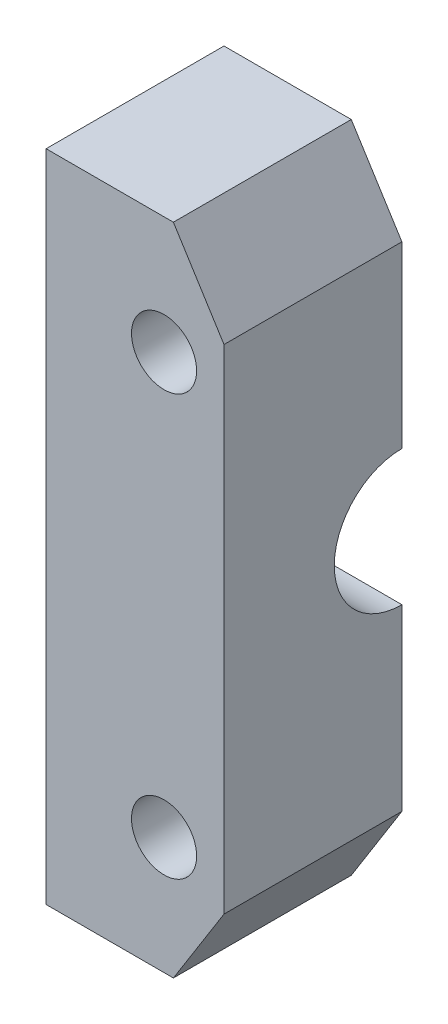
SolidWorks part; units mm, degrees
ref_plane "Front Plane" through (0, 0, 0) normal (0, 0, 1) x (1, 0, 0)
ref_plane "Top Plane" through (0, 0, 0) normal (0, 1, 0) x (1, 0, 0)
ref_plane "Right Plane" through (0, 0, 0) normal (1, 0, 0) x (0, 0, -1)
sketch "Sketch1" plane through (0, 0, 0) normal (0, 0, 1) x (1, 0, 0)
  line L1 (81.54, 23.365) -> (94.24, 23.365)
  line L2 (81.54, 23.365) -> (81.54, -23.365)
  line L3 (81.54, -23.365) -> (94.24, -23.365)
  line L4 (94.24, 23.365) -> (94.24, -23.365)
  line L9 (94.24, 4.826) -> (94.24, 17.6074)
  line L10 (94.24, 17.6074) -> (90.6266, 23.365)
  line L11 (77.2278, 38.2924) -> (72.7482, 36.0713)
  line L12 (72.7482, -36.0713) -> (77.2278, -38.2924)
  line L13 (90.6266, -23.365) -> (94.24, -17.6074)
  line L14 (94.24, -17.6074) -> (94.24, -4.826)
  line L15 (94.24, -4.826) -> (86.49, -4.826)
  line L16 (86.49, -4.826) -> (86.49, 4.826)
  line L17 (86.49, 4.826) -> (94.24, 4.826)
  line L18 (94.24, 4.826) -> (94.24, 17.6074)
  line L19 (94.24, 17.6074) -> (90.6266, 23.365)
  line L20 (77.2278, 38.2924) -> (72.7482, 36.0713)
  line L21 (72.7482, -36.0713) -> (77.2278, -38.2924)
  line L22 (90.6266, -23.365) -> (94.24, -17.6074)
  line L23 (94.24, -17.6074) -> (94.24, -4.826)
  line L24 (94.24, -4.826) -> (86.49, -4.826)
  line L25 (86.49, -4.826) -> (86.49, 4.826)
  line L26 (86.49, 4.826) -> (94.24, 4.826)
  circle A2 centre (89.96, 15) radius 2.325
  arc A3 (77.2278, 38.2924) -> (90.6266, 23.365) centre (110.7726, 54.9252) ccw
  arc A4 (72.7482, -36.0713) -> (72.7482, 36.0713) centre (0, 0) ccw
  arc A5 (90.6266, -23.365) -> (77.2278, -38.2924) centre (110.7726, -54.9252) ccw
  arc A6 (77.2278, 38.2924) -> (90.6266, 23.365) centre (110.7726, 54.9252) ccw
  arc A7 (72.7482, -36.0713) -> (72.7482, 36.0713) centre (0, 0) ccw
  arc A8 (90.6266, -23.365) -> (77.2278, -38.2924) centre (110.7726, -54.9252) ccw
  circle A9 centre (89.96, -15) radius 2.325
  circle A10 centre (89.96, 15) radius 2.5527 construction
  circle A11 centre (89.96, -15) radius 2.5527 construction
  dimension "D2" = 12.7
  dimension "D1" = 0
extrude "Boss-Extrude1" add sketch "Sketch1" along normal blind 12.7 contours L25 L26 L4 L19 L1 L2 L3 L22 L24 A9 A2 | L26 L25 L24 L4 region at (86.0833, 22.8808, 0) region at (90.365, 0, 0)
sketch "Sketch2" plane through (94.24, 0, 0) normal (1, 0, 0) x (0, 0, -1)
  line L4 (0, -17.6074) -> (0, 17.6074)
  line L5 (0, 17.6074) -> (-12.7, 17.6074)
  line L6 (-12.7, 17.6074) -> (-12.7, -17.6074)
  line L7 (-12.7, -17.6074) -> (0, -17.6074)
  line L8 (0, -17.6074) -> (0, 17.6074)
  line L9 (0, 17.6074) -> (-12.7, 17.6074)
  line L10 (-12.7, 17.6074) -> (-12.7, -17.6074)
  line L11 (-12.7, -17.6074) -> (0, -17.6074)
  arc A0 (0, 4.826) -> (0, -4.826) centre (0, 0) ccw construction
  arc A1 (0, 4.826) -> (0, -4.826) centre (0, 0) ccw
  circle A2 centre (0, 0) radius 4.826
  dimension "D1" = 0
extrude "Cut-Extrude1" cut sketch "Sketch2" against normal blind 8 contours A2
